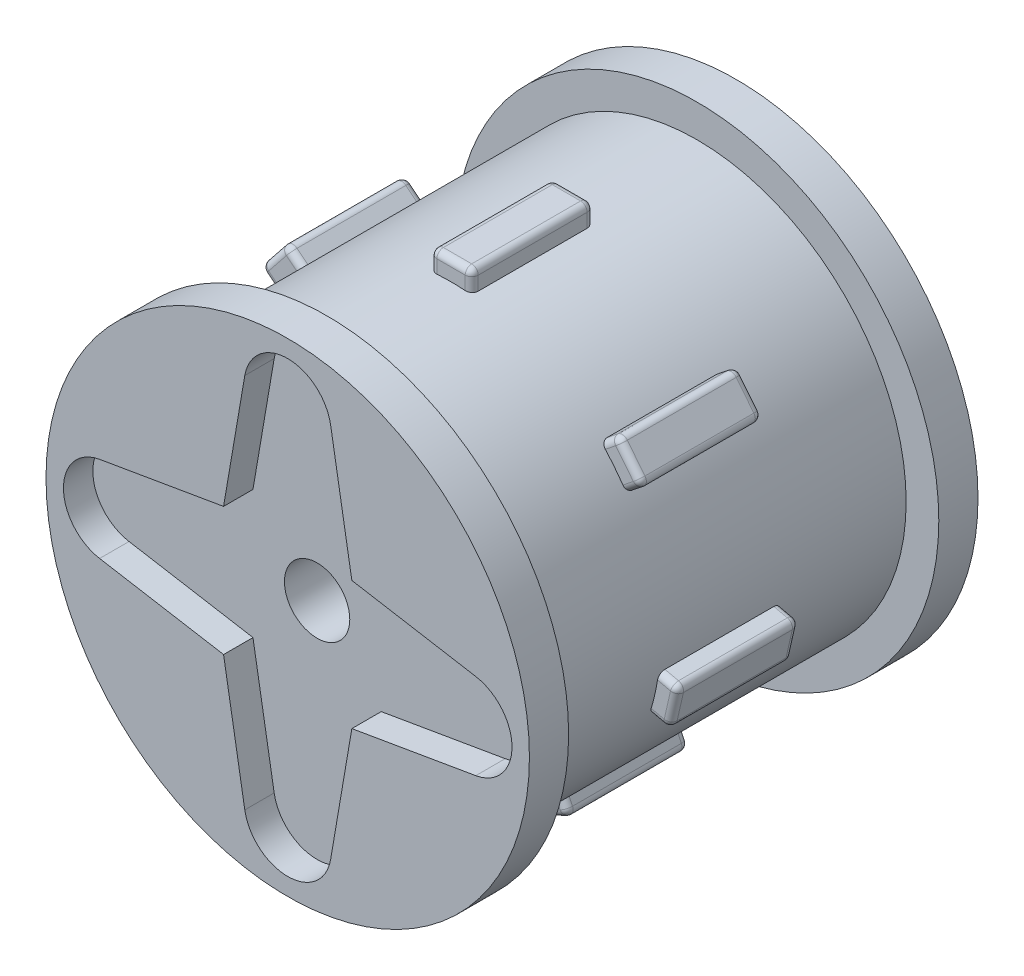
SolidWorks part; units mm, degrees
ref_plane "Ebene vorne" through (0, 0, 0) normal (0, 0, 1) x (1, 0, 0)
ref_plane "Ebene oben" through (0, 0, 0) normal (0, 1, 0) x (1, 0, 0)
ref_plane "Ebene rechts" through (0, 0, 0) normal (1, 0, 0) x (0, 0, -1)
sketch "Skizze1" plane through (0, 0, 0) normal (0, 0, 1) x (1, 0, 0)
  circle A0 centre (0, 0) radius 9.6
  dimension "D1" = 19.2
extrude "Aufsatz-Linear austragen1" add sketch "Skizze1" along normal blind 10.3 and the other way blind 10.3
ref_axis "Rotationsachse" through (0, 0, -10.3) along (0, 0, 1)
sketch "Skizze2" plane through (0, 0, 10.3) normal (0, 0, 1) x (1, 0, 0)
  circle A0 centre (0, 0) radius 11.1
  dimension "D1" = 22.2
extrude "Aufsatz-Linear austragen2" add sketch "Skizze2" against normal blind 1.8
sketch "Skizze3" plane through (0, 0, -10.3) normal (0, 0, -1) x (-1, 0, 0)
  circle A0 centre (0, 0) radius 11.1
  dimension "D1" = 22.2
extrude "Aufsatz-Linear austragen3" add sketch "Skizze3" against normal blind 1.8
sketch "Skizze4" plane through (0, 0, 10.3) normal (0, 0, 1) x (1, 0, 0)
  line L0 (-3.3513, 0.5735) -> (-1.9713, 8.6373)
  line L1 (3.3513, 0.5735) -> (1.9713, 8.6373)
  circle A0 centre (0, 0) radius 3.4
  circle A1 centre (0, 8.3) radius 2
  dimension "D1" = 6.8
  dimension "D3" = 4
  dimension "D2" = 8.3
extrude "Schnitt-Linear austragen1" cut sketch "Skizze4" against normal blind 1.35 contours A1 | A1 L0 A0 L1 | A0 region at (0, 4.7309, 10.3) region at (0, 0, 10.3) region at (0, 8.3, 10.3)
pattern_circular "Kreismuster1" count 4 over 360 about axis through (0, 0, -10.3) along (0, 0, 1) of "Schnitt-Linear austragen1"
sketch "Skizze8" plane through (0, 0, 0) normal (1, 0, 0) x (0, 0, -1)
  line L0 (10.3, 0) -> (10.3, 8)
  line L1 (10.3, -11.1) -> (10.3, 11.1) construction
  line L2 (10.3, 8) -> (8.5, 8)
  line L3 (8.5, 11.1) -> (8.5, -11.1) construction
  line L4 (8.5, 8) -> (-6.9411, 3.4654)
  line L6 (-6.9411, 3.4654) -> (-6.45, 0)
  line L7 (-6.45, 0) -> (10.3, 0)
  dimension "D1" = 8
  dimension "D2" = 3.5
  dimension "D3" = 16.75
revolve "Schnitt-Rotation1" cut sketch "Skizze8" angle 360 about axis through (0, 0, -10.3) along (0, 0, 1)
sketch "Skizze9" plane through (0, 0, 8.95) normal (0, 0, 1) x (1, 0, 0)
  circle A0 centre (0, 0) radius 1.5
  dimension "D1" = 3
extrude "Schnitt-Linear austragen2" cut sketch "Skizze9" against normal through all
ref_plane "Schnittebene_Zaehne" through (0, 0, 0) normal (0, 0, -1) x (-1, 0, 0)
sketch "Skizze11" plane through (0, 0, 0) normal (0, 0, -1) x (-1, 0, 0)
  line L0 (0, 0) -> (0, 12.664) construction
  line L6 (-0.95, 8.71) -> (0.95, 8.71)
  line L7 (-0.95, 8.71) -> (-0.95, 10.49)
  line L8 (-0.95, 10.49) -> (0.95, 10.49)
  line L9 (0.95, 8.71) -> (0.95, 10.49)
  line L10 (-0.95, 8.71) -> (0.95, 10.49) construction
  line L11 (-0.95, 10.49) -> (0.95, 8.71) construction
  circle A1 centre (0, 0) radius 9.6 construction
  point P3 (0, 9.6)
  dimension "D1" = 0.89
  dimension "D2" = 1.9
extrude "Aufsatz-Linear austragen4" add sketch "Skizze11" along normal blind 2.8 and the other way blind 2.8
pattern_circular "Kreismuster2" count 7 over 360 about axis through (0, 0, -10.3) along (0, 0, 1) of "Aufsatz-Linear austragen4"
fillet "Verrundung1" radius 0.3 56 edges at (8.2014, 6.5404, 2.8) (7.6091, 7.2831, 0) (8.2014, 6.5404, -2.8) (8.7937, 5.7977, 0) (-8.4274, 5.5055, 2.8) (-7.2428, 6.991, 2.8) (-7.2428, 6.991, -2.8) (-8.4274, 5.5055, -2.8) (-9.5588, -3.1562, -2.8) (-9.9816, -1.3038, -2.8) (-9.5588, -3.1562, 2.8) (-9.9816, -1.3038, 2.8) (-5.2041, -8.6168, -2.8) (-3.4922, -9.4412, -2.8) (-3.4922, -9.4412, 2.8) (-5.2041, -8.6168, 2.8) (5.2041, -8.6168, 2.8) (3.4922, -9.4412, 2.8) (3.4922, -9.4412, -2.8) (5.2041, -8.6168, -2.8) (9.5588, -3.1562, 2.8) (9.5588, -3.1562, -2.8) (9.9816, -1.3038, 2.8) (9.9816, -1.3038, -2.8) (8.4274, 5.5055, 2.8) (8.4274, 5.5055, -2.8) (7.2428, 6.991, -2.8) (7.2428, 6.991, 2.8) (0.95, 10.0214, 2.8) (0.95, 10.0214, -2.8) (-0.95, 10.0214, -2.8) (-0.95, 10.0214, 2.8) (10.4384, -1.4081, 0) (10.227, -2.3342, 2.8) (10.227, -2.3342, -2.8) (10.0156, -3.2604, 0) (4.5514, -9.4512, 2.8) (4.5514, -9.4512, -2.8) (5.4074, -9.039, 0) (3.6955, -9.8634, 0) (-4.5514, -9.4512, 2.8) (-4.5514, -9.4512, -2.8) (-5.4074, -9.039, 0) (-3.6955, -9.8634, 0) (-10.227, -2.3342, 2.8) (-10.227, -2.3342, -2.8) (-10.0156, -3.2604, 0) (-10.4384, -1.4081, 0) (-8.2014, 6.5404, -2.8) (-8.2014, 6.5404, 2.8) (-8.7937, 5.7977, 0) (-7.6091, 7.2831, 0) (0, 10.49, -2.8) (0, 10.49, 2.8) (0.95, 10.49, 0) (-0.95, 10.49, 0)
